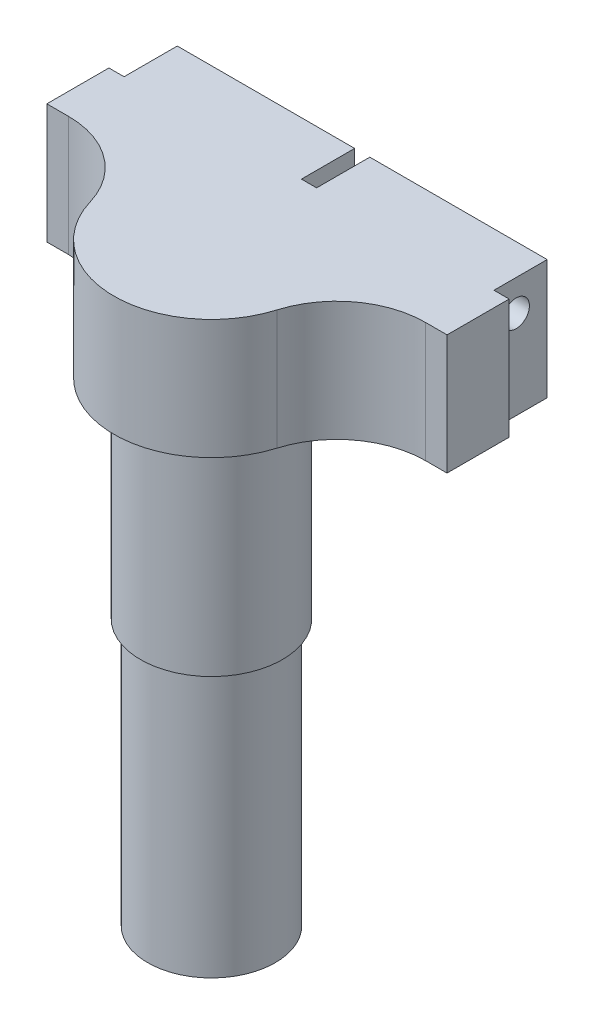
SolidWorks part; units mm, degrees
ref_plane "Front Plane" through (0, 0, 0) normal (0, 0, 1) x (1, 0, 0)
ref_plane "Top Plane" through (0, 0, 0) normal (0, 1, 0) x (1, 0, 0)
ref_plane "Right Plane" through (0, 0, 0) normal (1, 0, 0) x (0, 0, -1)
sketch "Sketch1" plane through (0, 0, 0) normal (0, 1, 0) x (1, 0, 0)
  line L0 (0, 0) -> (45.13, 0)
  line L1 (0, 0) -> (22.565, 0)
  line L2 (22.565, 0) -> (22.565, -8)
  line L3 (0, 0) -> (0, 7)
  line L4 (0, 7) -> (45.13, 7)
  line L5 (45.13, 7) -> (45.13, 0)
  circle A2 centre (22.565, -8) radius 11
  circle A3 centre (22.565, -8) radius 8
extrude "Boss-Extrude1" add sketch "Sketch1" along normal blind 10 contours A2 L0 L5 L4 L3 | L0 A2 L1 | A3 L1 A2 L0 region at (22.565, 0, -3.7498) region at (22.565, 0, -1.2152) region at (18.7901, 0, 0.2907)
sketch "Sketch2" plane through (0, 10, 0) normal (0, 1, 0) x (1, 0, 0)
  line L0 (0, 7) -> (1.71, 7)
  line L1 (0, 7) -> (45.13, 7) construction
  line L2 (1.71, 7) -> (21.71, 7)
  line L3 (21.71, 7) -> (23.42, 7)
  line L4 (23.42, 7) -> (43.42, 7)
  line L5 (43.42, 7) -> (45.13, 7)
  line L6 (0, 0) -> (0, 3)
  line L7 (0, 0) -> (0, 7) construction
  line L8 (0, 3) -> (45.13, 3)
  line L9 (45.13, 7) -> (45.13, 0) construction
  line L10 (1.71, 7) -> (1.71, 3)
  line L11 (1.71, 3) -> (21.71, 3)
  line L12 (21.71, 3) -> (21.71, 7)
  line L13 (23.42, 7) -> (23.42, 3)
  line L14 (23.42, 3) -> (43.42, 3)
  line L15 (43.42, 3) -> (43.42, 7)
  line L16 (0, 7) -> (0, 3)
  line L17 (45.13, 3) -> (45.13, 7)
  line M7 (45.13, 0) -> (45.13, 7)
  line M8 (45.13, 7) -> (0, 7)
  line M9 (0, 7) -> (0, 0)
extrude "Cut-Extrude1" cut sketch "Sketch2" against normal blind 10 contours L10 L8 M8 M9 | L13 L12 L8 M8 | L15 L8 M7 M8 region at (0.855, 10, -5) region at (22.565, 10, -5) region at (44.275, 10, -5)
sketch "Sketch3" plane through (0, 0, -7) normal (0, 0, -1) x (-1, 0, 0)
  line L0 (-43.42, 0) -> (-23.42, 0) construction
  line L1 (-23.42, 0) -> (-23.42, 10) construction
  line L2 (-23.42, 10) -> (-43.42, 10) construction
  line L3 (-43.42, 10) -> (-43.42, 0) construction
  line L4 (-21.71, 0) -> (-1.71, 0) construction
  line L5 (-1.71, 0) -> (-1.71, 10) construction
  line L6 (-1.71, 10) -> (-21.71, 10) construction
  line L7 (-21.71, 10) -> (-21.71, 0) construction
  line L8 (-43.42, 0) -> (-23.42, 0)
  line L9 (-23.42, 0) -> (-23.42, 10)
  line L10 (-23.42, 10) -> (-43.42, 10)
  line L11 (-43.42, 10) -> (-43.42, 0)
  line L12 (-21.71, 0) -> (-1.71, 0)
  line L13 (-1.71, 0) -> (-1.71, 10)
  line L14 (-1.71, 10) -> (-21.71, 10)
  line L15 (-21.71, 10) -> (-21.71, 0)
extrude "Boss-Extrude2" add sketch "Sketch3" along normal blind 3
sketch "Sketch4" plane through (0, 10, 0) normal (0, 1, 0) x (1, 0, 0)
  line L13 (21.71, 3) -> (21.71, 10)
  line L14 (21.71, 10) -> (1.71, 10)
  line L15 (1.71, 10) -> (1.71, 3)
  line L16 (1.71, 3) -> (0, 3)
  line L17 (0, 3) -> (0, 0)
  line L18 (0, 0) -> (15.0152, 0)
  line L19 (30.1148, 0) -> (45.13, 0)
  line L20 (45.13, 0) -> (45.13, 3)
  line L21 (45.13, 3) -> (43.42, 3)
  line L22 (43.42, 3) -> (43.42, 10)
  line L23 (43.42, 10) -> (23.42, 10)
  line L24 (23.42, 10) -> (23.42, 3)
  line L25 (23.42, 3) -> (21.71, 3)
  line L26 (21.71, 3) -> (21.71, 10)
  line L27 (21.71, 10) -> (1.71, 10)
  line L28 (1.71, 10) -> (1.71, 3)
  line L29 (1.71, 3) -> (0, 3)
  line L30 (0, 3) -> (0, 0)
  line L31 (0, 0) -> (15.0152, 0)
  line L32 (30.1148, 0) -> (45.13, 0)
  line L33 (45.13, 0) -> (45.13, 3)
  line L34 (45.13, 3) -> (43.42, 3)
  line L35 (43.42, 3) -> (43.42, 10)
  line L36 (43.42, 10) -> (23.42, 10)
  line L37 (23.42, 10) -> (23.42, 3)
  line L38 (23.42, 3) -> (21.71, 3)
  arc A4 (15.0152, 0) -> (30.1148, 0) centre (22.565, -8) ccw
  arc A7 (15.0152, 0) -> (30.1148, 0) centre (22.565, -8) ccw
  dimension "D1" = 0
extrude "Cut-Extrude2" cut sketch "Sketch4" against normal blind 3
sketch "Sketch6" plane through (0, 0, -10) normal (0, 0, -1) x (-1, 0, 0)
  line L0 (-23.42, 0) -> (-23.42, 7) construction
  line L1 (-23.42, 7) -> (-43.42, 7) construction
  line L2 (-43.42, 7) -> (-43.42, 0) construction
  line L3 (-43.42, 0) -> (-23.42, 0) construction
  line L4 (-1.71, 0) -> (-1.71, 7) construction
  line L5 (-1.71, 7) -> (-21.71, 7) construction
  line L6 (-21.71, 7) -> (-21.71, 0) construction
  line L7 (-21.71, 0) -> (-1.71, 0) construction
  line L8 (-23.42, 0) -> (-23.42, 7)
  line L9 (-23.42, 7) -> (-43.42, 7)
  line L10 (-43.42, 7) -> (-43.42, 0)
  line L11 (-43.42, 0) -> (-23.42, 0)
  line L12 (-1.71, 0) -> (-1.71, 7)
  line L13 (-1.71, 7) -> (-21.71, 7)
  line L14 (-21.71, 7) -> (-21.71, 0)
  line L15 (-21.71, 0) -> (-1.71, 0)
extrude "Boss-Extrude3" add sketch "Sketch6" along normal blind 2
sketch "Sketch7" plane through (1.71, 0, 0) normal (-1, 0, 0) x (0, 0, 1)
  line L0 (-3, 0) -> (-3, 7)
  line L1 (-3, 7) -> (-3, 3.5)
  line L2 (-3, 3.5) -> (-8.5, 3.5)
  circle A0 centre (-8.5, 3.5) radius 1.5
extrude "Cut-Extrude5" cut sketch "Sketch7" against normal blind 44 contours A0 region at (1.71, 3.5, -9.9576)
sketch "Sketch9" plane through (0, 0, -3) normal (0, 0, -1) x (-1, 0, 0)
  line L4 (-21.71, 7) -> (-23.42, 7)
  line L5 (-23.42, 7) -> (-23.42, 0)
  line L6 (-23.42, 0) -> (-21.71, 0)
  line L7 (-21.71, 0) -> (-21.71, 7)
  line L8 (-21.71, 7) -> (-23.42, 7)
  line L9 (-23.42, 7) -> (-23.42, 0)
  line L10 (-23.42, 0) -> (-21.71, 0)
  line L11 (-21.71, 0) -> (-21.71, 7)
  line L12 (0, 7) -> (-1.71, 7)
  line L13 (-1.71, 7) -> (-1.71, 0)
  line L14 (-1.71, 0) -> (0, 0)
  line L15 (0, 0) -> (0, 7)
  line L16 (0, 7) -> (-1.71, 7)
  line L17 (-1.71, 7) -> (-1.71, 0)
  line L18 (-1.71, 0) -> (0, 0)
  line L19 (0, 0) -> (0, 7)
  line L20 (-43.42, 7) -> (-45.13, 7)
  line L21 (-45.13, 7) -> (-45.13, 0)
  line L22 (-45.13, 0) -> (-43.42, 0)
  line L23 (-43.42, 0) -> (-43.42, 7)
  line L24 (-43.42, 7) -> (-45.13, 7)
  line L25 (-45.13, 7) -> (-45.13, 0)
  line L26 (-45.13, 0) -> (-43.42, 0)
  line L27 (-43.42, 0) -> (-43.42, 7)
  dimension "D1" = 0
  dimension "D2" = 0
  dimension "D3" = 0
extrude "Boss-Extrude4" add sketch "Sketch9" along normal blind 3
sketch "Sketch11" plane through (0, 7, 0) normal (0, 1, 0) x (1, 0, 0)
  line L13 (45.13, 6) -> (43.42, 6)
  line L14 (43.42, 6) -> (43.42, 12)
  line L15 (43.42, 12) -> (23.42, 12)
  line L16 (23.42, 12) -> (23.42, 6)
  line L17 (23.42, 6) -> (21.71, 6)
  line L18 (21.71, 6) -> (21.71, 12)
  line L19 (21.71, 12) -> (1.71, 12)
  line L20 (1.71, 12) -> (1.71, 6)
  line L21 (1.71, 6) -> (0, 6)
  line L22 (0, 6) -> (0, 0)
  line L23 (0, 0) -> (15.0152, 0)
  line L24 (30.1148, 0) -> (45.13, 0)
  line L25 (45.13, 0) -> (45.13, 6)
  line L26 (45.13, 6) -> (43.42, 6)
  line L27 (43.42, 6) -> (43.42, 12)
  line L28 (43.42, 12) -> (23.42, 12)
  line L29 (23.42, 12) -> (23.42, 6)
  line L30 (23.42, 6) -> (21.71, 6)
  line L31 (21.71, 6) -> (21.71, 12)
  line L32 (21.71, 12) -> (1.71, 12)
  line L33 (1.71, 12) -> (1.71, 6)
  line L34 (1.71, 6) -> (0, 6)
  line L35 (0, 6) -> (0, 0)
  line L36 (0, 0) -> (15.0152, 0)
  line L37 (30.1148, 0) -> (45.13, 0)
  line L38 (45.13, 0) -> (45.13, 6)
  circle A0 centre (22.565, -8) radius 8 construction
  circle A1 centre (22.565, -8) radius 8
  arc A4 (15.0152, 0) -> (30.1148, 0) centre (22.565, -8) ccw
  arc A7 (15.0152, 0) -> (30.1148, 0) centre (22.565, -8) ccw
  dimension "D1" = 0
extrude "Cut-Extrude6" cut sketch "Sketch11" against normal blind 1
sketch "Sketch12" plane through (0, 6, 0) normal (0, 1, 0) x (1, 0, 0)
  line L13 (45.13, 0) -> (45.13, 6)
  line L14 (45.13, 6) -> (43.42, 6)
  line L15 (43.42, 6) -> (43.42, 12)
  line L16 (43.42, 12) -> (23.42, 12)
  line L17 (23.42, 12) -> (23.42, 6)
  line L18 (23.42, 6) -> (21.71, 6)
  line L19 (21.71, 6) -> (21.71, 12)
  line L20 (21.71, 12) -> (1.71, 12)
  line L21 (1.71, 12) -> (1.71, 6)
  line L22 (1.71, 6) -> (0, 6)
  line L23 (0, 6) -> (0, 0)
  line L24 (0, 0) -> (15.0152, 0)
  line L25 (30.1148, 0) -> (45.13, 0)
  line L26 (45.13, 0) -> (45.13, 6)
  line L27 (45.13, 6) -> (43.42, 6)
  line L28 (43.42, 6) -> (43.42, 12)
  line L29 (43.42, 12) -> (23.42, 12)
  line L30 (23.42, 12) -> (23.42, 6)
  line L31 (23.42, 6) -> (21.71, 6)
  line L32 (21.71, 6) -> (21.71, 12)
  line L33 (21.71, 12) -> (1.71, 12)
  line L34 (1.71, 12) -> (1.71, 6)
  line L35 (1.71, 6) -> (0, 6)
  line L36 (0, 6) -> (0, 0)
  line L37 (0, 0) -> (15.0152, 0)
  line L38 (30.1148, 0) -> (45.13, 0)
  arc A4 (15.0152, 0) -> (30.1148, 0) centre (22.565, -8) ccw
  arc A7 (15.0152, 0) -> (30.1148, 0) centre (22.565, -8) ccw
  dimension "D1" = 0
extrude "Boss-Extrude6" add sketch "Sketch12" along normal blind 1
sketch "Sketch13" plane through (0, 6, 0) normal (0, -1, 0) x (1, 0, 0)
  circle A1 centre (22.565, 8) radius 8
  circle A2 centre (22.565, 8) radius 8
  dimension "D1" = 0
extrude "Boss-Extrude7" add sketch "Sketch13" along normal up to surface (6 mm away) up to face at (22.565, 0, -4.6429)
sketch "Sketch14" plane through (0, 0, 0) normal (0, -1, 0) x (1, 0, 0)
  circle A0 centre (22.565, 8) radius 8
extrude "Boss-Extrude8" add sketch "Sketch14" along normal blind 40
sketch "Sketch15" plane through (0, -40, 0) normal (0, -1, 0) x (1, 0, 0)
  circle A0 centre (22.565, 8) radius 7.5
extrude "Boss-Extrude9" add sketch "Sketch15" along normal blind 30
sketch "Sketch16" plane through (0, 0, 0) normal (0, -1, 0) x (1, 0, 0)
  line L13 (43.42, -12) -> (43.42, -6)
  line L14 (43.42, -6) -> (45.13, -6)
  line L15 (45.13, -6) -> (45.13, 0)
  line L16 (45.13, 0) -> (30.1148, 0)
  line L17 (15.0152, 0) -> (0, 0)
  line L18 (0, 0) -> (0, -6)
  line L19 (0, -6) -> (1.71, -6)
  line L20 (1.71, -6) -> (1.71, -12)
  line L21 (1.71, -12) -> (21.71, -12)
  line L22 (21.71, -12) -> (21.71, -6)
  line L23 (21.71, -6) -> (23.42, -6)
  line L24 (23.42, -6) -> (23.42, -12)
  line L25 (23.42, -12) -> (43.42, -12)
  line L26 (43.42, -12) -> (43.42, -6)
  line L27 (43.42, -6) -> (45.13, -6)
  line L28 (45.13, -6) -> (45.13, 0)
  line L29 (45.13, 0) -> (30.1148, 0)
  line L30 (15.0152, 0) -> (0, 0)
  line L31 (0, 0) -> (0, -6)
  line L32 (0, -6) -> (1.71, -6)
  line L33 (1.71, -6) -> (1.71, -12)
  line L34 (1.71, -12) -> (21.71, -12)
  line L35 (21.71, -12) -> (21.71, -6)
  line L36 (21.71, -6) -> (23.42, -6)
  line L37 (23.42, -6) -> (23.42, -12)
  line L38 (23.42, -12) -> (43.42, -12)
  arc A4 (30.1148, 0) -> (15.0152, 0) centre (22.565, 8) ccw
  arc A7 (30.1148, 0) -> (15.0152, 0) centre (22.565, 8) ccw
  dimension "D1" = 0
extrude "Boss-Extrude10" add sketch "Sketch16" along normal blind 6.5
sketch "Sketch17" plane through (0, -70, 0) normal (0, -1, 0) x (1, 0, 0)
  circle A0 centre (22.565, 8) radius 7
  circle A1 centre (22.565, 8) radius 15.7734
extrude "Cut-Extrude7" cut sketch "Sketch17" against normal up to surface (30 mm away) up to face at (22.565, -40, 0.5)
sketch "Sketch18" plane through (0, -70, 0) normal (0, -1, 0) x (1, 0, 0)
  circle A0 centre (22.565, 8) radius 7.1
extrude "Boss-Extrude11" add sketch "Sketch18" against normal up to surface (30 mm away) contours A0 up to face at (22.565, -40, 0)
sketch "Sketch19" plane through (0, -70, 0) normal (0, -1, 0) x (1, 0, 0)
  circle A0 centre (22.565, 8) radius 7.2
extrude "Boss-Extrude12" add sketch "Sketch19" against normal up to surface (30 mm away) up to face at (22.565, -40, 0.9)
sketch "Sketch20" plane through (0, -70, 0) normal (0, -1, 0) x (1, 0, 0)
  circle A0 centre (22.565, 8) radius 7.15
  circle A1 centre (22.565, 8) radius 12.8107
extrude "Cut-Extrude8" cut sketch "Sketch20" against normal up to surface (30 mm away) up to face at (22.565, -40, 0.8)
sketch "Sketch21" plane through (0, -70, 0) normal (0, -1, 0) x (1, 0, 0)
  circle A1 centre (22.565, 8) radius 7.15
  circle A2 centre (22.565, 8) radius 7.15
  dimension "D1" = 0
extrude "Cut-Extrude9" cut sketch "Sketch21" against normal blind 10
sketch "Sketch22" plane through (0, -40, 0) normal (0, -1, 0) x (1, 0, 0)
  circle A0 centre (22.565, 8) radius 7.15 construction
  circle A1 centre (22.565, 8) radius 8 construction
  circle A2 centre (22.565, 8) radius 7.15
  circle A3 centre (22.565, 8) radius 8
extrude "Cut-Extrude10" cut sketch "Sketch22" against normal blind 10
sketch "Sketch25" plane through (0, 7, 0) normal (0, 1, 0) x (1, 0, 0)
  line L0 (0, 6) -> (0, 3)
  line L1 (0, 6) -> (0, 0) construction
  line L2 (0, 3) -> (45.13, 3)
  line L3 (45.13, 0) -> (45.13, 6) construction
  line L4 (1.71, 6) -> (1.71, 3)
  line L5 (21.71, 6) -> (21.71, 3)
  line L6 (23.42, 6) -> (23.42, 3)
  line L7 (43.42, 6) -> (43.42, 3)
  line L8 (0, 6) -> (45.13, 6)
  line L9 (45.13, 6) -> (45.13, 3)
  line L10 (1.71, 12) -> (1.71, 9)
  line L11 (1.71, 12) -> (1.71, 6) construction
  line L12 (1.71, 9) -> (43.42, 9)
  line L13 (43.42, 6) -> (43.42, 12) construction
  line L14 (43.42, 9) -> (43.42, 12)
  line L15 (43.42, 12) -> (1.71, 12)
  circle A0 centre (22.565, -8) radius 8
  line M2 (45.13, 0) -> (45.13, 6)
  line M3 (45.13, 6) -> (43.42, 6)
  line M4 (43.42, 6) -> (43.42, 12)
  line M5 (43.42, 12) -> (23.42, 12)
  line M6 (23.42, 12) -> (23.42, 6)
  line M7 (23.42, 6) -> (21.71, 6)
  line M8 (21.71, 6) -> (21.71, 12)
  line M9 (21.71, 12) -> (1.71, 12)
  line M10 (1.71, 12) -> (1.71, 6)
  line M11 (1.71, 6) -> (0, 6)
  line M12 (0, 6) -> (0, 0)
extrude "Cut-Extrude13" cut sketch "Sketch25" against normal blind 21 contours L4 L2 M11 M12 | L12 M10 M8 M9 | L12 M6 M4 M5 | L6 L5 L2 M7 | L7 L2 M3 M2 region at (0.855, 7, -4.5) region at (22.565, 7, -4.5) region at (11.71, 7, -10.5) region at (44.275, 7, -4.5) region at (33.42, 7, -10.5)
sketch "Sketch26" plane through (1.71, 0, 0) normal (-1, 0, 0) x (0, 0, 1)
  line L0 (-3, 7) -> (-6, 7)
  line L1 (-9, 7) -> (-3, 7) construction
  line L2 (-9, 7) -> (-9, -6.5)
  circle A0 centre (-8.5, 3.5) radius 1.5
  arc M7 (-9, 4.9142) -> (-9, 2.0858) centre (-8.5, 3.5) cw
extrude "Boss-Extrude13" add sketch "Sketch26" against normal up to surface (20 mm away) contours L2 M7 region at (1.71, 3.5, -8.1233) up to face at (21.71, 1.3333, -6.6667)
sketch "Sketch27" plane through (43.42, 0, 0) normal (1, 0, 0) x (0, 0, -1)
  line L0 (9, 7) -> (9, -6.5)
  circle A1 centre (8.5, 3.5) radius 1.5
  arc M7 (9, 2.0858) -> (9, 4.9142) centre (8.5, 3.5) cw
extrude "Boss-Extrude14" add sketch "Sketch27" against normal up to surface (20 mm away) contours L0 M7 region at (43.42, 3.5, -8.1233) up to face at (23.42, 1.3333, -6.6667)
sketch "Sketch28" plane through (1.71, 0, 0) normal (-1, 0, 0) x (0, 0, 1)
  line L2 (-3, 7) -> (-3, 3.5)
  line L3 (-3, -6.5) -> (-3, 7) construction
  line L4 (-3, 3.5) -> (-5.5, 3.5)
  circle A0 centre (-5.5, 3.5) radius 1.5
extrude "Cut-Extrude14" cut sketch "Sketch28" against normal blind 50 contours A0 region at (1.71, 3.5, -6.9576)
sketch "Sketch29" plane through (0, 0, 0) normal (0, 0, 1) x (1, 0, 0)
  line L0 (0, 7) -> (0, -6.5)
  line L1 (0, -6.5) -> (45.13, -6.5)
  line L2 (45.13, -6.5) -> (45.13, 7)
  line L3 (45.13, 7) -> (0, 7)
extrude "Boss-Extrude15" add sketch "Sketch29" along normal blind 4
fillet "Fillet1" radius 10 2 edges at (32.812, 0.25, 4) (12.318, 0.25, 4)
fillet "Fillet2" radius 2 1 edges at (22.565, -6.5, 0)
sketch "Sketch30" plane through (0, -60, 0) normal (0, -1, 0) x (1, 0, 0)
  circle A0 centre (22.565, 8) radius 7.2
extrude "Boss-Extrude16" add sketch "Sketch30" against normal up to surface (30 mm away) up to face at (22.565, -30, 0.85)
